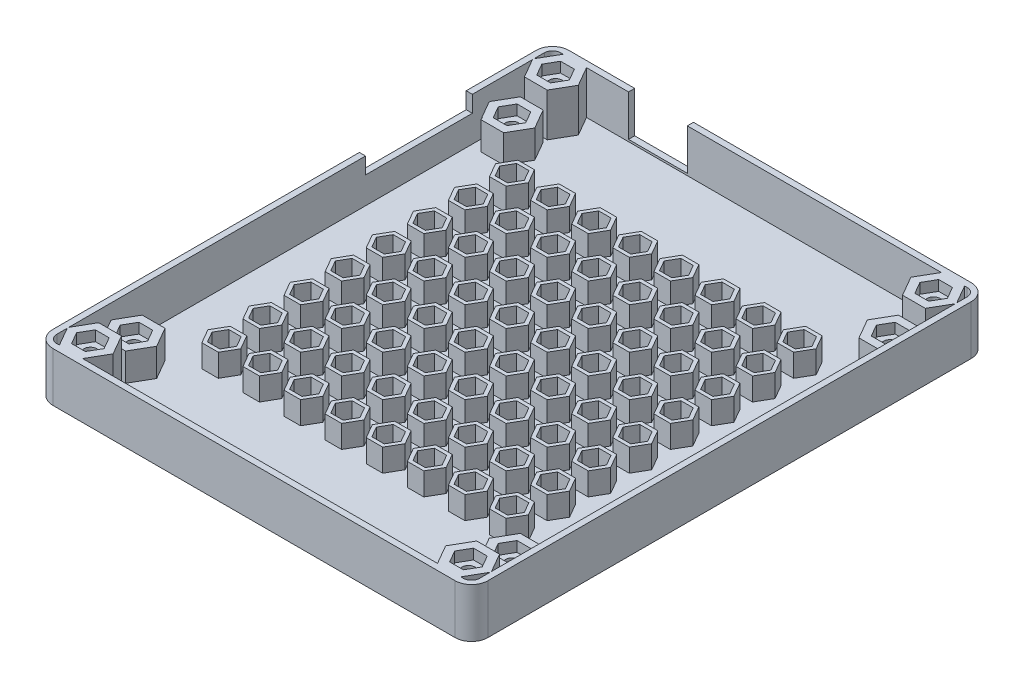
SolidWorks part; units mm, degrees
ref_plane "Přední rovina" through (0, 0, 0) normal (0, 0, 1) x (1, 0, 0)
ref_plane "Horní rovina" through (0, 0, 0) normal (0, 1, 0) x (1, 0, 0)
ref_plane "Pravá rovina" through (0, 0, 0) normal (1, 0, 0) x (0, 0, -1)
sketch "Skica1" plane through (0, 0, 0) normal (0, 1, 0) x (1, 0, 0)
  line L0 (0, 0) -> (-100, 100) construction
  line L1 (-50, 50) -> (50, 50) construction
  line L2 (-50, 50) -> (-50, -50) construction
  line L3 (-50, -50) -> (50, -50) construction
  line L4 (50, 50) -> (50, -50) construction
  line L5 (-50, 50) -> (50, -50) construction
  line L6 (-50, -50) -> (50, 50) construction
  line L7 (-47.6743, 43.1) -> (-44.3257, 43.1)
  line L8 (-44.3257, 43.1) -> (-42.6514, 46)
  line L9 (-42.6514, 46) -> (-44.3257, 48.9)
  line L10 (-44.3257, 48.9) -> (-47.6743, 48.9)
  line L11 (-47.6743, 48.9) -> (-49.3486, 46)
  line L12 (-49.3486, 46) -> (-47.6743, 43.1)
  line L13 (-48.7713, 41.2) -> (-43.2287, 41.2)
  line L14 (-43.2287, 41.2) -> (-40.4574, 46)
  line L15 (-40.4574, 46) -> (-43.2287, 50.8)
  line L16 (-43.2287, 50.8) -> (-48.7713, 50.8)
  line L17 (-48.7713, 50.8) -> (-51.5426, 46)
  line L18 (-51.5426, 46) -> (-48.7713, 41.2)
  line L19 (0, 81.3987) -> (0, -91.9033) construction
  line L20 (-42.6514, 56.6) -> (-44.3257, 59.5)
  line L21 (-44.3257, 59.5) -> (-47.6743, 59.5)
  line L22 (-47.6743, 59.5) -> (-49.3486, 56.6)
  line L23 (-49.3486, 56.6) -> (-47.6743, 53.7)
  line L24 (-47.6743, 53.7) -> (-44.3257, 53.7)
  line L25 (-44.3257, 53.7) -> (-42.6514, 56.6)
  line L26 (-48.7713, 51.8) -> (-43.2287, 51.8)
  line L27 (-43.2287, 51.8) -> (-40.4574, 56.6)
  line L28 (-40.4574, 56.6) -> (-43.2287, 61.4)
  line L29 (-43.2287, 61.4) -> (-48.7713, 61.4)
  line L30 (-48.7713, 61.4) -> (-51.5426, 56.6)
  line L31 (-51.5426, 56.6) -> (-48.7713, 51.8)
  line L36 (74.9355, -74.9355) -> (-74.9355, 74.9355) construction
  line L37 (74.9355, 74.9355) -> (-74.9355, -74.9355) construction
  line L38 (-52.9426, -62.8) -> (52.9426, -62.8)
  line L39 (-52.9426, -62.8) -> (-52.9426, 62.8)
  line L40 (-52.9426, 62.8) -> (52.9426, 62.8)
  line L41 (52.9426, -62.8) -> (52.9426, 62.8)
  line L42 (-52.9426, -62.8) -> (52.9426, 62.8) construction
  line L43 (-52.9426, 62.8) -> (52.9426, -62.8) construction
  line L44 (-106.951, 0) -> (125.2961, 0) construction
  line L45 (-46, 37.8836) -> (-46, 68.4593) construction
  line L47 (-51.4426, -61.3) -> (51.4426, -61.3)
  line L48 (-51.4426, -61.3) -> (-51.4426, 61.3)
  line L49 (-51.4426, 61.3) -> (51.4426, 61.3)
  line L50 (51.4426, -61.3) -> (51.4426, 61.3)
  line L51 (-51.4426, -61.3) -> (51.4426, 61.3) construction
  line L52 (-51.4426, 61.3) -> (51.4426, -61.3) construction
  circle A0 centre (-46, 46) radius 2.9 construction
  circle A1 centre (-46, 46) radius 4.8 construction
  circle A2 centre (-46, 56.6) radius 2.9 construction
  circle A3 centre (-46, 56.6) radius 4.8 construction
  circle A4 centre (-46, 46) radius 1.6
  circle A5 centre (-46, 56.6) radius 1.6
  point P0 (0, 0)
  point P7 (-41.8431, 43.6)
  dimension "D9" = 1.5
  dimension "D10" = 1.5
  dimension "D11" = 0.1
  dimension "D12" = 0.1
  dimension "D13" = 3.2
  dimension "D14" = 3.2
  dimension "D1" = 100
  dimension "D2" = 100
  dimension "D3" = 5.8
  dimension "D4" = 4
  dimension "D5" = 9.6
  dimension "D6" = 5.8
  dimension "D7" = 9.6
  dimension "D8" = 1
extrude "Přidat vysunutím25" add sketch "Skica1" against normal blind 3 contours L49 L48 L30 | L20 L21 L22 L23 L24 L25 | L7 L8 L9 L10 L11 L12 | L48 L47 L50 L49 | L13 L14 L15 L16 L17 L18 | L26 L27 L28 L29 L30 L31 region at (-50.5714, 0, -59.7911)
extrude "Přidat vysunutím26" add sketch "Skica1<21>" against normal blind 3 and the other way blind 10.5 contours L38 L41 L40 L39 L50 L47 L48 L18 L17 L31 L30 L49 L29 L28 | L18 L48 L17 | L31 L48 L30 | L30 L49 L28 L29 region at (-51.4759, 0, -46) region at (-51.4759, 0, -56.6) region at (-46, 0, -61.3498) region at (-52.7783, 0, 0)
sketch "Skica1<21>" plane through (0, 0, 0) normal (0, 1, 0) x (1, 0, 0) same geometry as "Skica1"
extrude "Přidat vysunutím28" add sketch "Skica1<23>" along normal blind 6.8 contours L48 L18 L13 L14 L15 L16 L17 L12 L11 L10 L9 L8 L7 | L18 L48 L17 region at (-49.9806, 0, -43.5863) region at (-51.4759, 0, -46)
sketch "Skica1<23>" plane through (0, 0, 0) normal (0, 1, 0) x (1, 0, 0) same geometry as "Skica1"
extrude "Přidat vysunutím29" add sketch "Skica1<24>" along normal blind 4.3 contours L11 L12 L7 L8 L9 L10 region at (-48.4347, 0, -44.5943)
sketch "Skica1<24>" plane through (0, 0, 0) normal (0, 1, 0) x (1, 0, 0) same geometry as "Skica1"
pattern_linear "LinPole3" count 2 spacing 92 along (1, 0, 0) count 2 spacing 92 along (0, 0, 1) of "Přidat vysunutím28", "Přidat vysunutím29"
extrude "Přidat vysunutím30" add sketch "Skica1<25>" along normal blind 10.5 contours L49 L30 L48 L31 L26 L27 L28 L25 L24 L23 L22 L21 L20 | L30 L49 L28 L29 | L31 L48 L30 region at (-51.2973, 0, -56.6) region at (-51.4759, 0, -56.6) region at (-46, 0, -61.3498)
sketch "Skica1<25>" plane through (0, 0, 0) normal (0, 1, 0) x (1, 0, 0) same geometry as "Skica1"
extrude "Přidat vysunutím31" add sketch "Skica1<26>" along normal blind 8 contours L24 L25 L20 L21 L22 L23 A5 region at (-43.5653, 0, -55.1943)
sketch "Skica1<26>" plane through (0, 0, 0) normal (0, 1, 0) x (1, 0, 0) same geometry as "Skica1"
pattern_linear "LinPole4" count 2 spacing 92 along (1, 0, 0) count 2 spacing 113.2 along (0, 0, 1) of "Přidat vysunutím31", "Přidat vysunutím30"
fillet "Zaoblit4" radius 4 4 edges at (-52.9426, 3.75, 62.8) (52.9426, 3.75, 62.8) (52.9426, 3.75, -62.8) (-52.9426, 3.75, -62.8)
sketch "Skica9" plane through (-52.9426, 0, 0) normal (-1, 0, 0) x (0, 0, 1)
  line L0 (58.8, 10.5) -> (-58.8, 10.5) construction
  line L1 (-15.8, 6.5) -> (-41.8, 6.5)
  line L2 (-15.8, 6.5) -> (-15.8, 10.5)
  line L3 (-15.8, 10.5) -> (-41.8, 10.5)
  line L4 (-41.8, 6.5) -> (-41.8, 10.5)
  line L5 (-15.8, 6.5) -> (-41.8, 10.5) construction
  line L6 (-15.8, 10.5) -> (-41.8, 6.5) construction
  line L7 (-62.8, -3) -> (-62.8, 10.5) construction
  point P0 (-28.8, 8.5)
  dimension "D1" = 26
  dimension "D2" = 21
  dimension "D3" = 4
extrude "Odebrat vysunutím1" cut sketch "Skica9" against normal blind 4 contours L4 L3 L2 L1
sketch "Skica10" plane through (0, 0, -62.8) normal (0, 0, -1) x (-1, 0, 0)
  line L0 (48.9426, 10.5) -> (-48.9426, 10.5) construction
  line L1 (18.6426, 0.5) -> (32.9426, 0.5)
  line L2 (18.6426, 0.5) -> (18.6426, 10.5)
  line L3 (18.6426, 10.5) -> (32.9426, 10.5)
  line L4 (32.9426, 0.5) -> (32.9426, 10.5)
  line L5 (52.9426, 10.5) -> (52.9426, -3) construction
  dimension "D1" = 10
  dimension "D2" = 14.3
  dimension "D3" = 20
extrude "Odebrat vysunutím2" cut sketch "Skica10" against normal blind 5
sketch "Skica11" plane through (0, 0, 0) normal (0, 1, 0) x (1, 0, 0)
  line L0 (-43.171, 61.3) -> (43.171, 61.3) construction
  line L1 (-35, -35) -> (35, -35) construction
  line L2 (-35, -35) -> (-35, 35) construction
  line L3 (-35, 35) -> (35, 35) construction
  line L4 (35, -35) -> (35, 35) construction
  line L5 (-35, -35) -> (35, 35) construction
  line L6 (-35, 35) -> (35, -35) construction
  line L7 (-33.5, 32.4019) -> (-32, 35)
  line L8 (-32, 35) -> (-33.5, 37.5981)
  line L9 (-33.5, 37.5981) -> (-36.5, 37.5981)
  line L10 (-36.5, 37.5981) -> (-38, 35)
  line L11 (-38, 35) -> (-36.5, 32.4019)
  line L12 (-36.5, 32.4019) -> (-33.5, 32.4019)
  line L13 (-33, 31.5359) -> (-31, 35)
  line L14 (-31, 35) -> (-33, 38.4641)
  line L15 (-33, 38.4641) -> (-37, 38.4641)
  line L16 (-37, 38.4641) -> (-39, 35)
  line L17 (-39, 35) -> (-37, 31.5359)
  line L18 (-37, 31.5359) -> (-33, 31.5359)
  circle A0 centre (-35, 35) radius 2.5981 construction
  circle A1 centre (-35, 35) radius 3.4641 construction
  point P0 (0, 0)
  dimension "D1" = 70
  dimension "D2" = 3
  dimension "D3" = 4
extrude "Přidat vysunutím32" add sketch "Skica11" along normal blind 5.5
pattern_linear "LinPole5" count 8 spacing 10 along (1, 0, 0) count 8 spacing 10 along (0, 0, 1) of "Přidat vysunutím32"
sketch "Skica12" plane through (52.9426, 0, 0) normal (1, 0, 0) x (0, 0, -1)
  line L0 (-58.8, -3) -> (58.8, -3) construction
  line L1 (-68.1521, -1.5) -> (66.6031, -1.5)
  line L2 (-68.1521, -1.5) -> (-68.1521, -12.5491)
  line L3 (-68.1521, -12.5491) -> (66.6031, -12.5491)
  line L4 (66.6031, -1.5) -> (66.6031, -12.5491)
  dimension "D1" = 1.5
extrude "Odebrat vysunutím3" cut sketch "Skica12" against normal through all
fillet "Zaoblit5" radius 2 4 edges at (-51.4426, 5.25, 61.3) (51.4426, 5.25, 61.3) (51.4426, 5.25, -61.3) (-51.4426, 5.25, -61.3)
